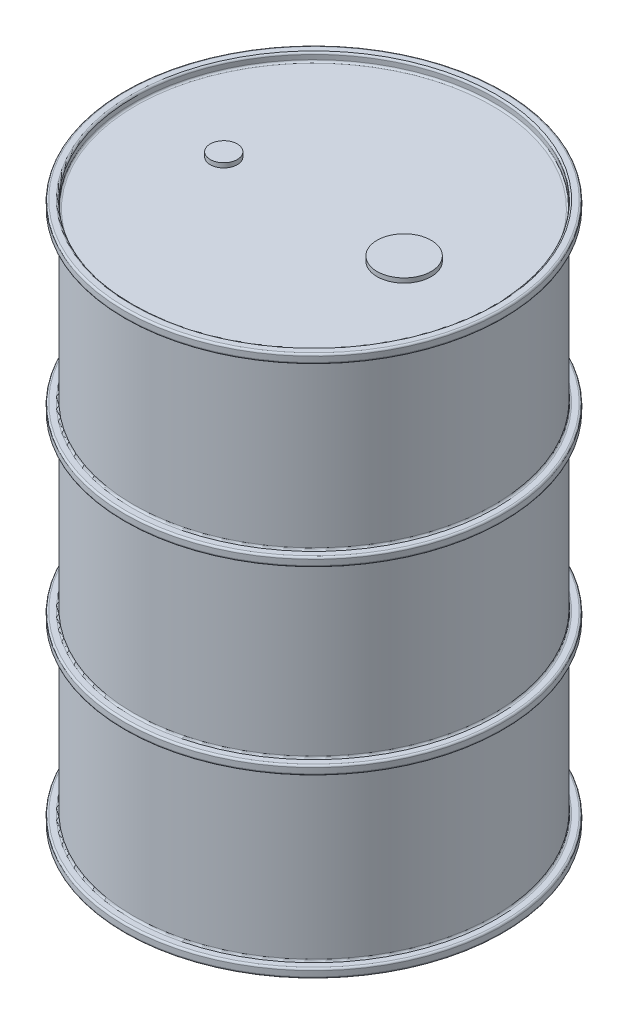
SolidWorks part; units mm, degrees
material "ABS"
ref_plane "Alzado" through (0, 0, 0) normal (0, 0, 1) x (1, 0, 0)
ref_plane "Planta" through (0, 0, 0) normal (0, 1, 0) x (1, 0, 0)
ref_plane "Vista lateral" through (0, 0, 0) normal (1, 0, 0) x (0, 0, -1)
sketch "Croquis1" plane through (0, 0, 0) normal (0, 1, 0) x (1, 0, 0)
  circle A0 centre (0, 0) radius 10.5
  circle A1 centre (0, 0) radius 10
  dimension "D1" = 20
  dimension "D2" = 21
extrude "Saliente-Extruir1" add sketch "Croquis1" along normal blind 30 contours A1
extrude "Saliente-Extruir2" add sketch "Croquis1<5>" along normal blind 0.5
sketch "Croquis1<5>" plane through (0, 0, 0) normal (0, 1, 0) x (1, 0, 0) same geometry as "Croquis1"
extrude "Saliente-Extruir3" add sketch "Croquis1<6>" along normal mid plane 0.5 from offset 10
sketch "Croquis1<6>" plane through (0, 0, 0) normal (0, 1, 0) x (1, 0, 0) same geometry as "Croquis1"
extrude "Saliente-Extruir4" add sketch "Croquis1<7>" along normal mid plane 0.5 from offset 20
sketch "Croquis1<7>" plane through (0, 0, 0) normal (0, 1, 0) x (1, 0, 0) same geometry as "Croquis1"
extrude "Saliente-Extruir5" add sketch "Croquis1<8>" against normal blind 0.5 from offset 30
sketch "Croquis1<8>" plane through (0, 0, 0) normal (0, 1, 0) x (1, 0, 0) same geometry as "Croquis1"
sketch "Croquis2" plane through (0, 30, 0) normal (0, 1, 0) x (1, 0, 0)
  circle A0 centre (0, 0) radius 10
  dimension "D1" = 20
extrude "Cortar-Extruir1" cut sketch "Croquis2" against normal blind 0.45
extrude "Cortar-Extruir2" cut sketch "Croquis2<2>" along normal blind 0.45 from offset 30 offset against normal yes
sketch "Croquis2<2>" plane through (0, 30, 0) normal (0, 1, 0) x (1, 0, 0) same geometry as "Croquis2"
fillet "Redondeo2" radius 0.1 18 edges at (0, 0.45, 10) (0, 0, 10) (0, 0, 10.5) (0, 0.5, 10.5) (0, 0.5, 10) (0, 9.75, 10) (0, 9.75, 10.5) (0, 10.25, 10.5) (0, 10.25, 10) (0, 19.75, 10) (0, 19.75, 10.5) (0, 20.25, 10.5) (0, 20.25, 10) (0, 29.55, 10) (0, 30, 10) (0, 30, 10.5) (0, 29.5, 10.5) (0, 29.5, 10)
sketch "Croquis3" plane through (0, 29.55, 0) normal (0, 1, 0) x (1, 0, 0)
  circle A0 centre (-5, 0) radius 0.75
  circle A1 centre (5, 0) radius 1.5
  dimension "D1" = 3
  dimension "D2" = 1.5
  dimension "D3" = 5
  dimension "D4" = 5
extrude "Saliente-Extruir6" add sketch "Croquis3" along normal blind 0.25
